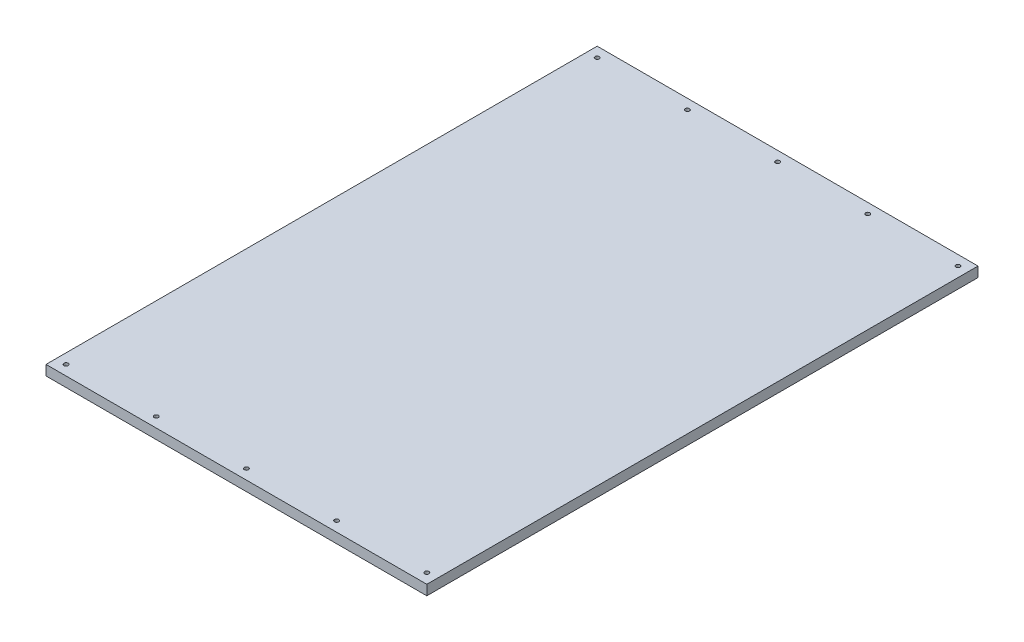
SolidWorks part; units mm, degrees
ref_plane "Front Plane" through (0, 0, 0) normal (0, 0, 1) x (1, 0, 0)
ref_plane "Top Plane" through (0, 0, 0) normal (0, 1, 0) x (1, 0, 0)
ref_plane "Right Plane" through (0, 0, 0) normal (1, 0, 0) x (0, 0, -1)
sketch "Sketch1" plane through (0, 0, 0) normal (0, 1, 0) x (1, 0, 0)
  line L1 (-190, 275) -> (190, 275)
  line L2 (-190, 275) -> (-190, -275)
  line L3 (-190, -275) -> (190, -275)
  line L4 (190, 275) -> (190, -275)
  line L5 (-190, 275) -> (190, -275) construction
  line L6 (-190, -275) -> (190, 275) construction
  point P0 (0, 0)
  dimension "D1" = 550
  dimension "D2" = 380
extrude "Boss-Extrude1" add sketch "Sketch1" along normal blind 10
sketch "Sketch2" plane through (0, 10, 0) normal (0, 1, 0) x (1, 0, 0)
  line L0 (-190, 275) -> (-190, 265) construction
  line L1 (-190, 275) -> (-190, -275) construction
  line L2 (-190, 265) -> (190, 265) construction
  line L3 (-55, 0) -> (55, 0) construction
  circle A0 centre (0, 265) radius 2.1
  circle A1 centre (90, 265) radius 2.1
  circle A2 centre (180, 265) radius 2.1
  circle A3 centre (-90, 265) radius 2.1
  circle A4 centre (-180, 265) radius 2.1
  circle A5 centre (180, -265) radius 2.1
  circle A6 centre (90, -265) radius 2.1
  circle A7 centre (0, -265) radius 2.1
  circle A8 centre (-90, -265) radius 2.1
  circle A9 centre (-180, -265) radius 2.1
  dimension "D3" = 4.2
  dimension "D4" = 4.2
  dimension "D5" = 4.2
  dimension "D6" = 4.2
  dimension "D7" = 4.2
  dimension "D1" = 10
  dimension "D2" = 380
  dimension "D8" = 10
  dimension "D9" = 90
  dimension "D10" = 10
  dimension "D11" = 90
extrude "Cut-Extrude1" cut sketch "Sketch2" against normal blind 10
